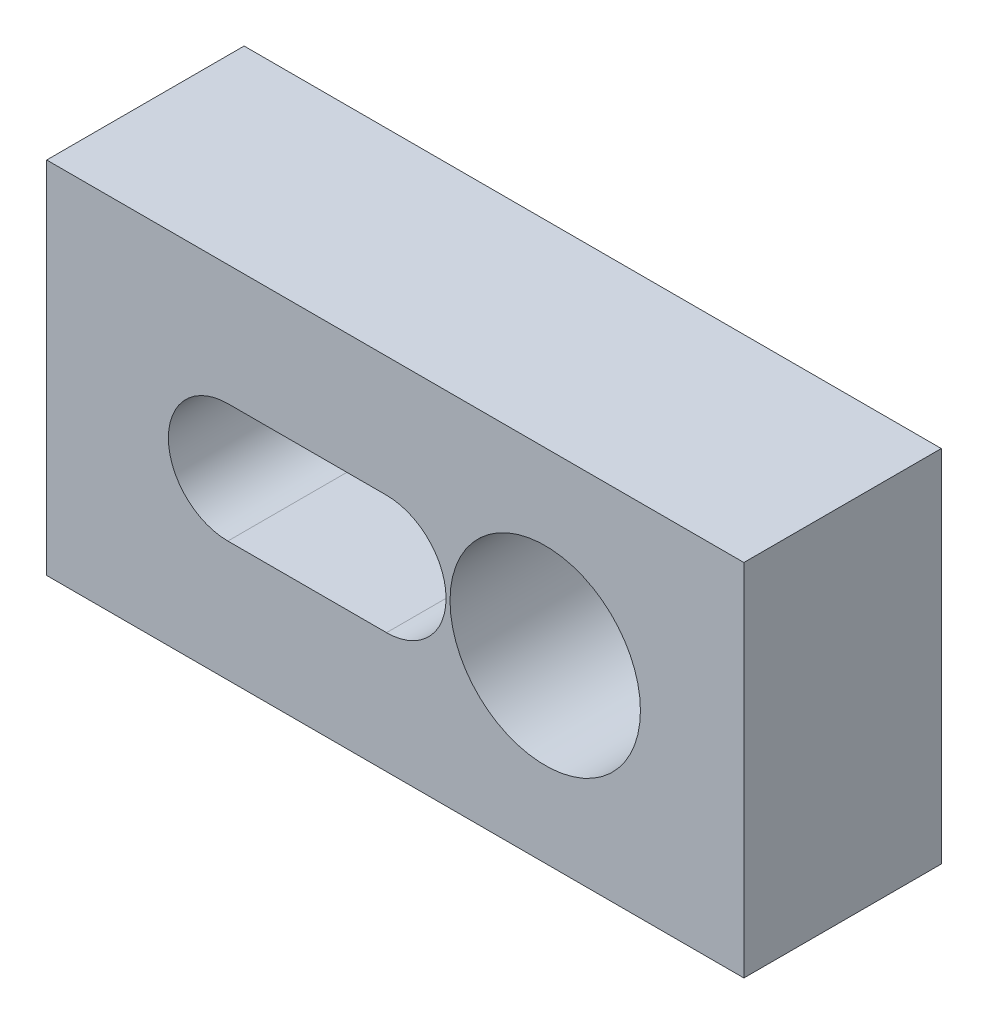
SolidWorks part; units mm, degrees
ref_plane "Front Plane" through (0, 0, 0) normal (0, 0, 1) x (1, 0, 0)
ref_plane "Top Plane" through (0, 0, 0) normal (0, 1, 0) x (1, 0, 0)
ref_plane "Right Plane" through (0, 0, 0) normal (1, 0, 0) x (0, 0, -1)
sketch "Sketch1" plane through (0, 0, 0) normal (0, 1, 0) x (1, 0, 0)
  line L1 (-39.0999, 16.0935) -> (16.7001, 16.0935)
  line L2 (-39.0999, 16.0935) -> (-39.0999, 0.2935)
  line L3 (-39.0999, 0.2935) -> (16.7001, 0.2935)
  line L4 (16.7001, 16.0935) -> (16.7001, 0.2935)
  dimension "D1" = 55.8
  dimension "D2" = 15.8
extrude "Boss-Extrude1" add sketch "Sketch1" along normal blind 28.8
sketch "Sketch2" plane through (0, 0, -0.2935) normal (0, 0, 1) x (1, 0, 0)
  line L0 (-39.0999, 0) -> (16.7001, 0) construction
  line L1 (-11.8999, 14.4) -> (-24.5999, 14.4) construction
  line L2 (-11.8999, 9.6375) -> (-24.5999, 9.6375)
  line L3 (-11.8999, 19.1625) -> (-24.5999, 19.1625)
  line L4 (16.7001, 28.8) -> (16.7001, 0) construction
  circle A0 centre (0.8001, 14.4) radius 7.62
  arc A1 (-11.8999, 9.6375) -> (-11.8999, 19.1625) centre (-11.8999, 14.4) ccw
  arc A2 (-24.5999, 19.1625) -> (-24.5999, 9.6375) centre (-24.5999, 14.4) ccw
  point P6 (-18.2499, 14.4)
  dimension "D4" = 15.24
  dimension "D5" = 4.7625
  dimension "D1" = 14.4
  dimension "D2" = 12.7
  dimension "D3" = 12.7
  dimension "D6" = 15.9
extrude "Cut-Extrude1" cut sketch "Sketch2" against normal blind 12.7
sketch "Sketch4" plane through (0, 0, -16.0935) normal (0, 0, -1) x (-1, 0, 0)
  line L0 (-16.7001, 28.8) -> (-16.7001, 0) construction
  circle A6 centre (-0.8001, 14.4) radius 2.7781
  circle A7 centre (11.8999, 14.4) radius 1.8415
  circle A8 centre (24.5999, 14.4) radius 1.8415
  dimension "D1" = 5.5563
  dimension "D2" = 3.683
  dimension "D3" = 3.683
  dimension "D4" = 12.7
  dimension "D5" = 12.7
  dimension "D6" = 15.9
extrude "Cut-Extrude2" cut sketch "Sketch4" against normal blind 12.7
sketch "Sketch5" plane through (0, 0, -16.0935) normal (0, 0, -1) x (-1, 0, 0)
  line L2 (24.5999, 19.1625) -> (11.8999, 19.1625)
  line L3 (11.8999, 9.6375) -> (24.5999, 9.6375)
  line L12 (24.5999, 19.1625) -> (11.8999, 19.1625)
  line L13 (11.8999, 9.6375) -> (24.5999, 9.6375)
  arc A2 (11.8999, 19.1625) -> (11.8999, 9.6375) centre (11.8999, 14.4) ccw
  arc A3 (24.5999, 9.6375) -> (24.5999, 19.1625) centre (24.5999, 14.4) ccw
  arc A4 (11.8999, 19.1625) -> (11.8999, 9.6375) centre (11.8999, 14.4) ccw
  arc A5 (24.5999, 9.6375) -> (24.5999, 19.1625) centre (24.5999, 14.4) ccw
  dimension "D2" = 0
extrude "Cut-Extrude6" cut sketch "Sketch5" against normal blind 1.905
